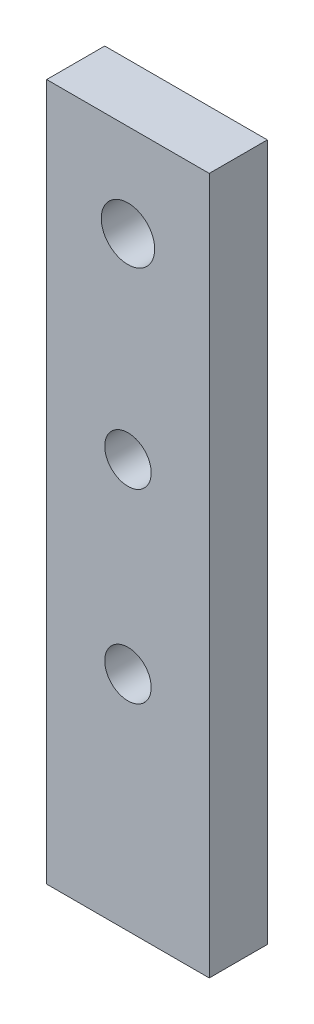
SolidWorks part; units mm, degrees
ref_plane "Front Plane" through (0, 0, 0) normal (0, 0, 1) x (1, 0, 0)
ref_plane "Top Plane" through (0, 0, 0) normal (0, 1, 0) x (1, 0, 0)
ref_plane "Right Plane" through (0, 0, 0) normal (1, 0, 0) x (0, 0, -1)
sketch "Sketch3" plane through (0, 0, 0) normal (0, 1, 0) x (1, 0, 0)
  line L7 (0, -3.556) -> (8.89, -3.556)
  line L9 (0, -3.556) -> (8.89, -3.556)
  line L10 (0, -3.556) -> (0, -6.731)
  line L11 (0, -6.731) -> (8.89, -6.731)
  line L12 (8.89, -3.556) -> (8.89, -6.731)
  dimension "D3" = 3.175
extrude "Boss-Extrude2" add sketch "Sketch3" along normal blind 38.1 contours L12 L7 L10 L11 region at (4.445, 0, 5.1435)
sketch "Sketch4" plane through (0, 0, 6.731) normal (0, 0, 1) x (1, 0, 0)
  line L0 (4.445, 38.1) -> (4.445, 33.02)
  line L1 (0, 38.1) -> (8.89, 38.1) construction
  line L2 (4.445, 0) -> (4.445, 3.175)
  line L3 (0, 0) -> (8.89, 0) construction
  line L4 (4.445, 3.175) -> (4.445, 12.1691)
  line L5 (4.445, 12.1691) -> (4.445, 22.3291)
  circle A0 centre (4.445, 33.02) radius 1.4605
  circle A1 centre (4.445, 12.1691) radius 1.27
  circle A2 centre (4.445, 22.3291) radius 1.27
  dimension "D2" = 2.921
  dimension "D4" = 2.54
  dimension "D5" = 2.54
  dimension "D1" = 5.08
  dimension "D3" = 3.175
  dimension "D6" = 10.16
extrude "Cut-Extrude1" cut sketch "Sketch4" against normal through all contours A0 | A1 | A2
